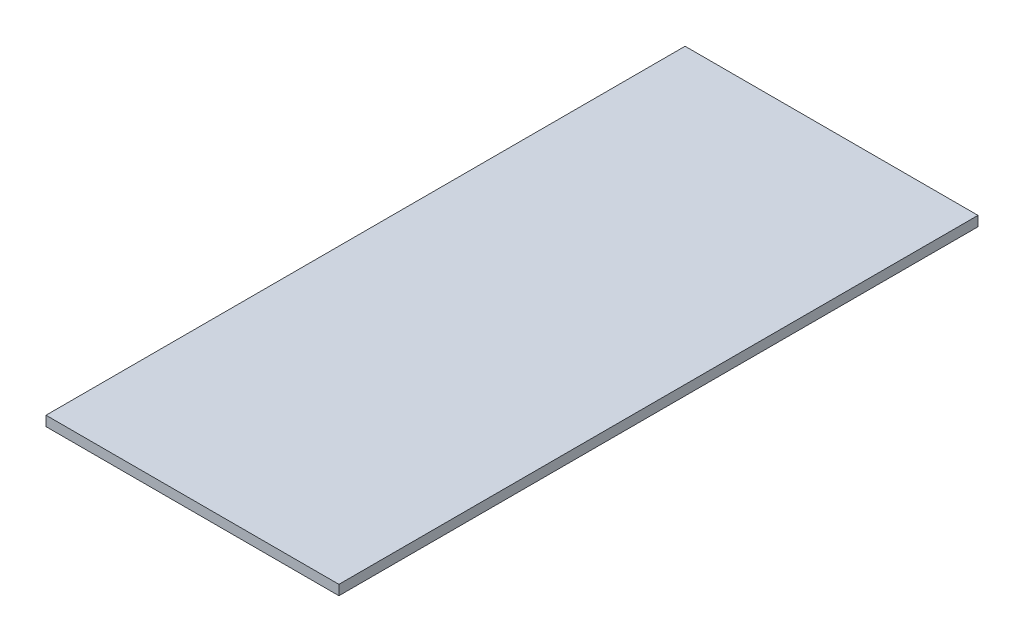
SolidWorks part; units mm, degrees
ref_plane "Front Plane" through (0, 0, 0) normal (0, 0, 1) x (1, 0, 0)
ref_plane "Top Plane" through (0, 0, 0) normal (0, 1, 0) x (1, 0, 0)
ref_plane "Right Plane" through (0, 0, 0) normal (1, 0, 0) x (0, 0, -1)
sketch "Sketch1" plane through (0, 0, 0) normal (0, 1, 0) x (1, 0, 0)
  line L1 (0, 0) -> (-69.85, 0)
  line L2 (0, 0) -> (0, 152.4)
  line L3 (0, 152.4) -> (-69.85, 152.4)
  line L4 (-69.85, 0) -> (-69.85, 152.4)
  dimension "D1" = 152.4
  dimension "D2" = 69.85
extrude "Boss-Extrude1" add sketch "Sketch1" along normal blind 2.3622
